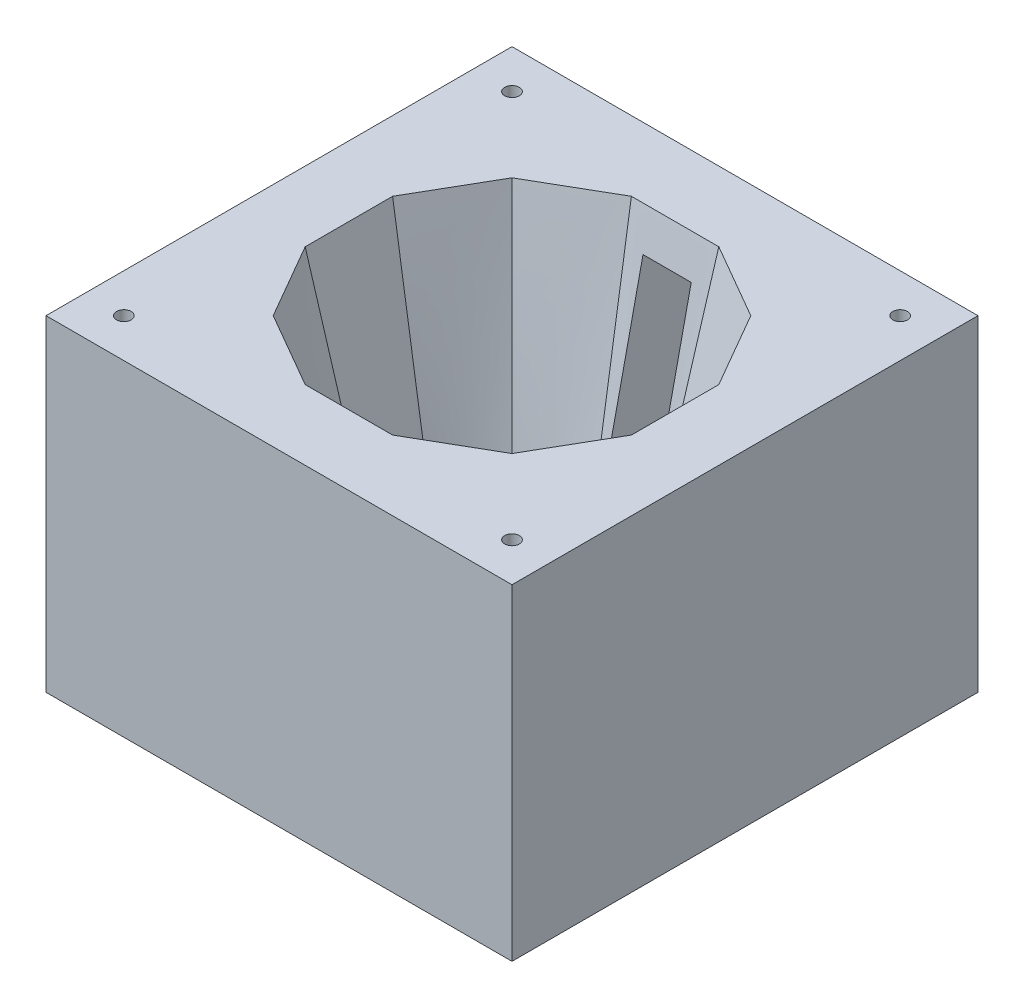
SolidWorks part; units mm, degrees
material "Nylon 101"
ref_plane "Front Plane" through (0, 0, 0) normal (0, 0, 1) x (1, 0, 0)
ref_plane "Top Plane" through (0, 0, 0) normal (0, 1, 0) x (1, 0, 0)
ref_plane "Right Plane" through (0, 0, 0) normal (1, 0, 0) x (0, 0, -1)
sketch "id" plane through (0, 0, 0) normal (0, 1, 0) x (1, 0, 0)
  circle A0 centre (0, 0) radius 25.4
  dimension "D1" = 50.8
ref_plane "Outside face" through (0, 88.9, 0) normal (0, 1, 0) x (1, 0, 0)
sketch "od" plane through (0, 88.9, 0) normal (0, 1, 0) x (1, 0, 0)
  line L1 (44.45, -11.9103) -> (44.45, 11.9103)
  line L2 (44.45, 11.9103) -> (32.5397, 32.5397)
  line L3 (32.5397, 32.5397) -> (11.9103, 44.45)
  line L4 (11.9103, 44.45) -> (-11.9103, 44.45)
  line L5 (-11.9103, 44.45) -> (-32.5397, 32.5397)
  line L6 (-32.5397, 32.5397) -> (-44.45, 11.9103)
  line L7 (-44.45, 11.9103) -> (-44.45, -11.9103)
  line L8 (-44.45, -11.9103) -> (-32.5397, -32.5397)
  line L9 (-32.5397, -32.5397) -> (-11.9103, -44.45)
  line L10 (-11.9103, -44.45) -> (11.9103, -44.45)
  line L11 (11.9103, -44.45) -> (32.5397, -32.5397)
  line L12 (32.5397, -32.5397) -> (44.45, -11.9103)
  circle A0 centre (0, 0) radius 44.45 construction
  dimension "D1" = 88.9
sketch "Sketch3" plane through (0, 88.9, 0) normal (0, 1, 0) x (1, 0, 0)
  line L0 (-48.895, 0) -> (48.895, 0) construction
  line L1 (-63.5, -63.5) -> (63.5, -63.5)
  line L2 (-63.5, -63.5) -> (-63.5, 63.5)
  line L3 (-63.5, 63.5) -> (63.5, 63.5)
  line L4 (63.5, -63.5) -> (63.5, 63.5)
  line L5 (-63.5, -63.5) -> (63.5, 63.5) construction
  line L6 (-63.5, 63.5) -> (63.5, -63.5) construction
  line L7 (0, -48.895) -> (0, 48.895) construction
  circle A0 centre (-52.8934, 52.8934) radius 2
  circle A1 centre (-52.8934, -52.8934) radius 2
  circle A2 centre (52.8934, -52.8934) radius 2
  circle A3 centre (52.8934, 52.8934) radius 2
  point P0 (0, 0)
  point P6 (-53.0546, 53.0546)
  dimension "D2" = 4
  dimension "D1" = 127
  dimension "D3" = 15
extrude "Boss-Extrude1" add sketch "Sketch3" against normal up to surface (88.9 mm away) contours L1 L4 L3 L2 A1 A0 A2 A3 | A1 | A2 | A3 | A0 region at (0, 88.9, 0) region at (-52.8934, 88.9, -52.8934) region at (-52.8934, 88.9, 52.8934) region at (52.8934, 88.9, 52.8934) region at (52.8934, 88.9, -52.8934) up to plane "Top Plane"
extrude "Cut-Extrude1" cut sketch "Sketch3<3>" against normal blind 30 contours A1 | A2 | A3 | A0 region at (-52.8934, 88.9, -52.8934) region at (-52.8934, 88.9, 52.8934) region at (52.8934, 88.9, 52.8934) region at (52.8934, 88.9, -52.8934)
sketch "Sketch3<3>" plane through (0, 88.9, 0) normal (0, 1, 0) x (1, 0, 0) same geometry as "Sketch3"
loft "Cut-Loft1" cut profiles "od", "id" connector at (-32.5397, 88.9, 32.5397) connector at (-6.8408, 0, 24.4615)
sketch "Sketch5" plane through (0, 88.9, 0) normal (0, 1, 0) x (1, 0, 0)
  line L0 (-63.5, 63.5) -> (63.5, 63.5) construction
  line L1 (-6.574, 63.5) -> (6.574, 63.5)
  line L2 (-6.574, 63.5) -> (-6.574, 24.5345)
  line L4 (6.574, 63.5) -> (6.574, 24.5345)
  arc A0 (6.574, 24.5345) -> (-6.574, 24.5345) centre (0, 0) ccw construction
  arc A1 (6.574, 24.5345) -> (-6.574, 24.5345) centre (0, 0) ccw
  point P1 (-6.2113, 24.6288)
  point P9 (6.574, 24.186)
extrude "Cut-Extrude3" cut sketch "Sketch5" against normal through all from offset 10 offset against normal yes
equation "\"id\"= 2in"
equation "\"od\"= 4in"
equation "\"h\"= 3.5in"
equation "\"D1@id\" = \"id\""
equation "\"D1@od\" = \"h\""
